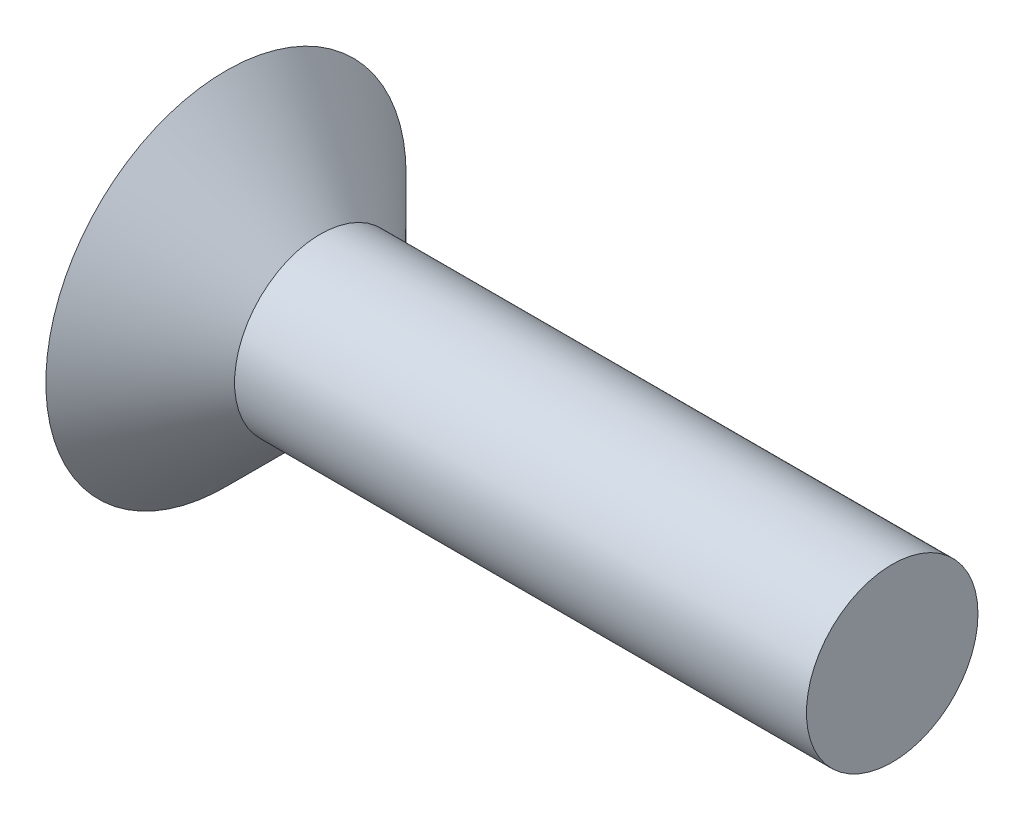
SolidWorks part; units mm, degrees
ref_plane "Спереди" through (0, 0, 0) normal (0, 0, 1) x (1, 0, 0)
ref_plane "Сверху" through (0, 0, 0) normal (0, 1, 0) x (1, 0, 0)
ref_plane "Справа" through (0, 0, 0) normal (1, 0, 0) x (0, 0, -1)
sketch "Эскиз1" plane through (0, 0, 0) normal (0, 0, 1) x (1, 0, 0)
  line L0 (0, 0) -> (0, 3.15)
  line L1 (0, 3.15) -> (1.65, 1.5)
  line L2 (1.65, 1.5) -> (11.65, 1.5)
  line L3 (11.65, 1.5) -> (11.65, 0)
  line L4 (11.65, 0) -> (0, 0)
  line L5 (0, 0) -> (-2.697, 0) construction
  dimension "D1" = 3
  dimension "D2" = 45
  dimension "D3" = 1.65
  dimension "D4" = 10
revolve "Повернуть1" add sketch "Эскиз1" angle 360 about L5
cosmetic thread "Условное изображение резьбы1" parameters "D2"=2
